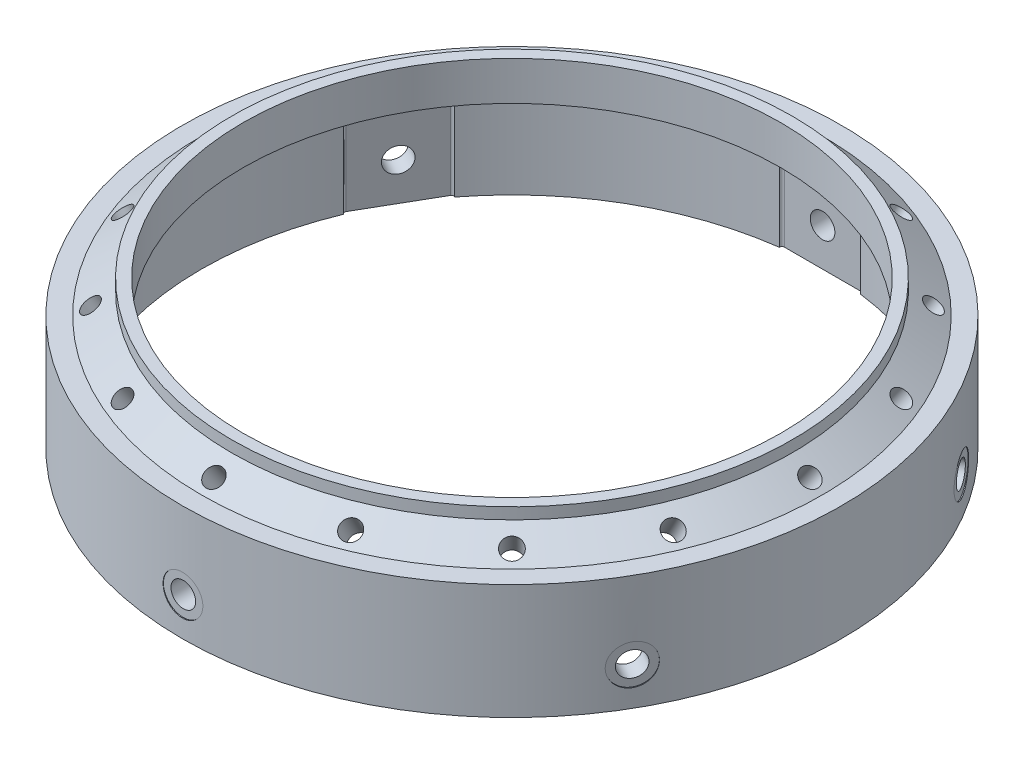
SolidWorks part; units mm, degrees
material "6063-T6"
ref_plane "Front Plane" through (0, 0, 0) normal (0, 0, 1) x (1, 0, 0)
ref_plane "Top Plane" through (0, 0, 0) normal (0, 1, 0) x (1, 0, 0)
ref_plane "Right Plane" through (0, 0, 0) normal (1, 0, 0) x (0, 0, -1)
sketch "Sketch1" plane through (0, 0, 0) normal (0, 0, 1) x (1, 0, 0)
  line L9 (0, 0) -> (0, -25.8501) construction
  line L18 (-87, 1) -> (-82, 1)
  line L19 (-82, 1) -> (-74, 6.6017)
  line L20 (-74, 6.6017) -> (-74, 9.6017)
  line L21 (-74, 9.6017) -> (-71, 9.6017)
  line L33 (-71, 9.6017) -> (-71, -0.6981)
  line L34 (-82, -8.4004) -> (-71, -0.6981)
  line L39 (-82, -8.4004) -> (-82, -29.4004)
  line L41 (-82, -29.4004) -> (-87, -29.4004)
  line L42 (-87, -29.4004) -> (-87, 1)
  dimension "D8" = 3
  dimension "D11" = 3
  dimension "D12" = 5
revolve "Revolve1" add sketch "Sketch1" angle 360 about L9
sketch "Sketch2" plane through (0, 0, 0) normal (0, 0, 1) x (1, 0, 0)
  line L0 (-74, 6.6017) -> (-82, 1) construction
  line L1 (-74, 6.6017) -> (-74, 1) construction
  line L2 (-74, 1) -> (-82, 1) construction
  point P4 (-78.671, 3.331)
  dimension "D1" = 4.671
hole_wizard "Ø4.2mm Dowel Hole1" positions "3DSketch1" profile "Sketch3" hole size "Ø5.0" standard "DIN" end condition up to next
sketch3d "3DSketch1"
  point P0 (-78.671, 3.331, 0)
sketch "Sketch3" plane through (-78.671, 3.331, 0) normal (0, 0, 1) x (-0.8192, -0.5736, 0)
  line L0 (0, 0) -> (0, 7.7004)
  line L1 (0, 7.7004) -> (2.5, 7.7004)
  line L2 (2.5, 7.7004) -> (2.5, 0)
  line L5 (2.5, 0) -> (0, 0)
  line L11 (0, -6.35) -> (0, 107.95) construction
  dimension "Thru Hole Dia." = 5
  dimension "Thru Hole Depth" = 7.7004
pattern_circular "CirPattern1" count 16 over 360 about axis through (0, 6.6017, 0) along (0, 1, 0) of "Ø4.2mm Dowel Hole1"
sketch "Szkic4" plane through (0, -29.4004, 0) normal (0, -1, 0) x (-1, 0, 0)
  line L0 (-4, -87) -> (4, -87)
  line L1 (0, -87) -> (0, -84.0434)
  line L2 (0, -84.0434) -> (4, -85.4333)
  line L3 (4, -85.4333) -> (4, -87)
  line L4 (-4, -85.4333) -> (-4, -87)
  line L5 (0, -84.0434) -> (-4, -85.4333)
  line L31 (-77.3442, -40.0359) -> (-73.3442, -46.9641)
  line L32 (-71.9874, -46.1808) -> (-73.3442, -46.9641)
  line L33 (-72.7837, -42.0217) -> (-71.9874, -46.1808)
  line L34 (-72.7837, -42.0217) -> (-75.9874, -39.2526)
  line L35 (-75.9874, -39.2526) -> (-77.3442, -40.0359)
  line L36 (-73.3442, 46.9641) -> (-77.3442, 40.0359)
  line L37 (-75.9874, 39.2526) -> (-77.3442, 40.0359)
  line L38 (-72.7837, 42.0217) -> (-75.9874, 39.2526)
  line L39 (-72.7837, 42.0217) -> (-71.9874, 46.1808)
  line L40 (-71.9874, 46.1808) -> (-73.3442, 46.9641)
  line L41 (4, 87) -> (-4, 87)
  line L42 (-4, 85.4333) -> (-4, 87)
  line L43 (0, 84.0434) -> (-4, 85.4333)
  line L44 (0, 84.0434) -> (4, 85.4333)
  line L45 (4, 85.4333) -> (4, 87)
  line L46 (77.3442, 40.0359) -> (73.3442, 46.9641)
  line L47 (71.9874, 46.1808) -> (73.3442, 46.9641)
  line L48 (72.7837, 42.0217) -> (71.9874, 46.1808)
  line L49 (72.7837, 42.0217) -> (75.9874, 39.2526)
  line L50 (75.9874, 39.2526) -> (77.3442, 40.0359)
  line L51 (73.3442, -46.9641) -> (77.3442, -40.0359)
  line L52 (75.9874, -39.2526) -> (77.3442, -40.0359)
  line L53 (72.7837, -42.0217) -> (75.9874, -39.2526)
  line L54 (72.7837, -42.0217) -> (71.9874, -46.1808)
  line L55 (71.9874, -46.1808) -> (73.3442, -46.9641)
  line L56 (0, 82) -> (-10.1, 82)
  line L57 (-10.1, 82) -> (-10.1, 79.6554)
  line L58 (-10.1, 79.6554) -> (10.1, 79.6554)
  line L59 (10.1, 79.6554) -> (10.1, 82)
  line L60 (10.1, 82) -> (0, 82)
  circle A0 centre (0, 0) radius 87 construction
  circle A1 centre (0, 0) radius 82 construction
  point P37 (0, 0)
  point P38 (0, 0)
  dimension "D1" = 6
sketch "Szkic2" plane through (0, 0, 0) normal (0, 0, 1) x (1, 0, 0)
  line L0 (0, -29.4004) -> (0, -19.4004)
  line L1 (-87, -29.4004) -> (87, -29.4004) construction
  circle A0 centre (0, -19.4004) radius 3.25
  dimension "D1" = 6.5
extrude "Wytnij-wyciągnięcie1" cut sketch "Szkic2" along normal blind 103 contours A0
pattern_circular "Szyk kołowy1" count 6 over 360 about axis through (0, 0, 0) along (0, 1, 0) of "Wytnij-wyciągnięcie1" reverse direction yes
extrude "Wytnij-wyciągnięcie2" cut sketch "Szkic4" against normal blind 21 contours L60 L56 L57 L58 L59
pattern_circular "Szyk kołowy2" count 6 over 360 about axis through (0, 0, 0) along (0, 1, 0) of "Wytnij-wyciągnięcie2" reverse direction yes
ref_plane "Plane1" through (0, 0, 87) normal (0, 0, 1) x (1, 0, 0)
sketch "Sketch4" plane through (0, 0, 87) normal (0, 0, 1) x (1, 0, 0)
  circle A0 centre (0, -19.4004) radius 3.25 construction
  circle A1 centre (0, -19.4004) radius 3.25
  circle A2 centre (0, -19.4004) radius 5.25
  dimension "D1" = 10.5
extrude "Cut-Extrude1" cut sketch "Sketch4" against normal blind 0.25 and the other way through all
pattern_circular "CirPattern2" count 6 over 360 about axis through (0, 0, 0) along (0, 1, 0) of "Cut-Extrude1" reverse direction yes
sketch "Sketch5" plane through (-71.0141, 0, 41) normal (0.866, 0, -0.5) x (-0.5, 0, -0.866)
  line L0 (-10.1, -29.4004) -> (-10.72, -29.4004)
  line L1 (-10.72, -29.4004) -> (-10.72, -8.4004)
  line L2 (-10.72, -8.4004) -> (-10.1, -8.4004)
  line L3 (10.1, -8.4004) -> (10.72, -8.4004)
  line L4 (10.72, -8.4004) -> (10.72, -29.4004)
  line L5 (-10.1, -29.4004) -> (10.1, -29.4004)
  line L6 (10.1, -29.4004) -> (10.1, -8.4004)
  line L7 (10.1, -8.4004) -> (0, -8.4004)
  line L8 (0, -8.4004) -> (-10.1, -8.4004)
  line L9 (-10.1, -8.4004) -> (-10.1, -29.4004)
  line L10 (-10.1, -29.4004) -> (10.1, -29.4004)
  line L11 (10.1, -29.4004) -> (10.1, -8.4004)
  line L12 (10.1, -8.4004) -> (0, -8.4004)
  line L13 (0, -8.4004) -> (-10.1, -8.4004)
  line L14 (-10.1, -8.4004) -> (-10.1, -29.4004)
  line L15 (10.72, -29.4004) -> (10.1, -29.4004)
  line M10 (10.1, -29.4004) -> (10.1, -8.4004)
  line M13 (-10.1, -8.4004) -> (-10.1, -29.4004)
  dimension "D2" = 0.62
  dimension "D3" = 0.62
  dimension "D1" = 0
extrude "Cut-Extrude3" cut sketch "Sketch5" along normal blind 10 contours L2 L1 L0 M13 | L15 L4 L3 M10 region at (-65.8091, -18.9004, 50.0153) region at (-76.2191, -18.9004, 31.9847)
fillet "Fillet1" radius 0.62 2 edges at (-76.3741, -18.9004, 31.7162) (-65.6541, -18.9004, 50.2838)
pattern_circular "CirPattern3" count 6 over 360 about axis through (0, -0.6981, 0) along (0, 1, 0) of "Fillet1", "Cut-Extrude3"
equation "\"D1@Sketch2\"=4+cos(35)*cos(35)"
